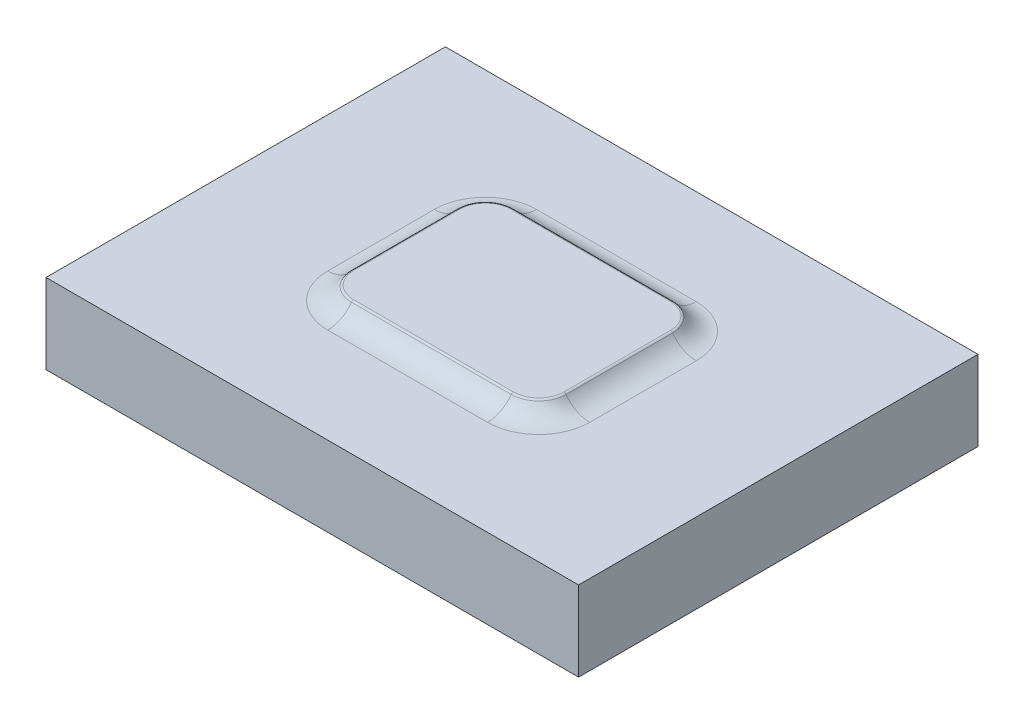
SolidWorks part; units mm, degrees
ref_plane "前视基准面" through (0, 0, 0) normal (0, 0, 1) x (1, 0, 0)
ref_plane "上视基准面" through (0, 0, 0) normal (0, 1, 0) x (1, 0, 0)
ref_plane "右视基准面" through (0, 0, 0) normal (1, 0, 0) x (0, 0, -1)
sketch "草图1" plane through (0, 0, 0) normal (0, 1, 0) x (1, 0, 0)
  line L1 (10, 7.5) -> (-10, 7.5)
  line L2 (10, 7.5) -> (10, -7.5)
  line L3 (10, -7.5) -> (-10, -7.5)
  line L4 (-10, 7.5) -> (-10, -7.5)
  line L5 (10, 7.5) -> (-10, -7.5) construction
  line L6 (10, -7.5) -> (-10, 7.5) construction
  point P0 (0, 0)
  dimension "D1" = 20
  dimension "D2" = 15
extrude "凸台-拉伸1" add sketch "草图1" along normal blind 3
sketch "草图2" plane through (0, 3, 0) normal (0, 1, 0) x (1, 0, 0)
  line L1 (4, 3) -> (-4, 3)
  line L2 (4, 3) -> (4, -3)
  line L3 (4, -3) -> (-4, -3)
  line L4 (-4, 3) -> (-4, -3)
  line L5 (4, 3) -> (-4, -3) construction
  line L6 (4, -3) -> (-4, 3) construction
  point P0 (0, 0)
  dimension "D1" = 8
  dimension "D2" = 6
extrude "凸台-拉伸2" add sketch "草图2" along normal blind 0.5
fillet "圆角1" radius 1 4 edges at (-4, 3.25, -3) (4, 3.25, -3) (4, 3.25, 3) (-4, 3.25, 3)
fillet "圆角2" radius 1.1 8 edges at (3.7071, 3, 2.7071) (0, 3, 3) (-3.7071, 3, 2.7071) (-4, 3, 0) (-3.7071, 3, -2.7071) (0, 3, -3) (3.7071, 3, -2.7071) (4, 3, 0)
fillet "圆角3" radius 0.1 8 edges at (3.7071, 3.5, 2.7071) (0, 3.5, 3) (-3.7071, 3.5, 2.7071) (-4, 3.5, 0) (-3.7071, 3.5, -2.7071) (0, 3.5, -3) (3.7071, 3.5, -2.7071) (4, 3.5, 0)
sketch "方向草图" plane through (0, 3, 0) normal (0, 1, 0) x (1, 0, 0)
  line L0 (4.922, 2) -> (4.922, -2) construction
  line L1 (3, -3.922) -> (-3, -3.922) construction
  line L2 (-4.922, -2) -> (-4.922, 2) construction
  line L3 (-3, 3.922) -> (3, 3.922) construction
  line L4 (-10, 7.5) -> (-10, -7.5) construction
  line L5 (-10, -7.5) -> (10, -7.5) construction
  line L6 (10, -7.5) -> (10, 7.5) construction
  line L7 (10, 7.5) -> (-10, 7.5) construction
  line L8 (4.922, 2) -> (4.922, -2)
  line L9 (3, -3.922) -> (-3, -3.922)
  line L10 (-4.922, -2) -> (-4.922, 2)
  line L11 (-3, 3.922) -> (3, 3.922)
  line L12 (-10, 7.5) -> (-10, -7.5) construction
  line L13 (-10, -7.5) -> (10, -7.5) construction
  line L14 (10, -7.5) -> (10, 7.5) construction
  line L15 (10, 7.5) -> (-10, 7.5) construction
  arc A0 (3, -3.922) -> (4.922, -2) centre (3, -2) ccw construction
  arc A1 (-4.922, -2) -> (-3, -3.922) centre (-3, -2) ccw construction
  arc A2 (-3, 3.922) -> (-4.922, 2) centre (-3, 2) ccw construction
  arc A3 (4.922, 2) -> (3, 3.922) centre (3, 2) ccw construction
  arc A4 (3, -3.922) -> (4.922, -2) centre (3, -2) ccw
  arc A5 (-4.922, -2) -> (-3, -3.922) centre (-3, -2) ccw
  arc A6 (-3, 3.922) -> (-4.922, 2) centre (-3, 2) ccw
  arc A7 (4.922, 2) -> (3, 3.922) centre (3, 2) ccw
  point P14 (0, 0)
other "成形工具1"
